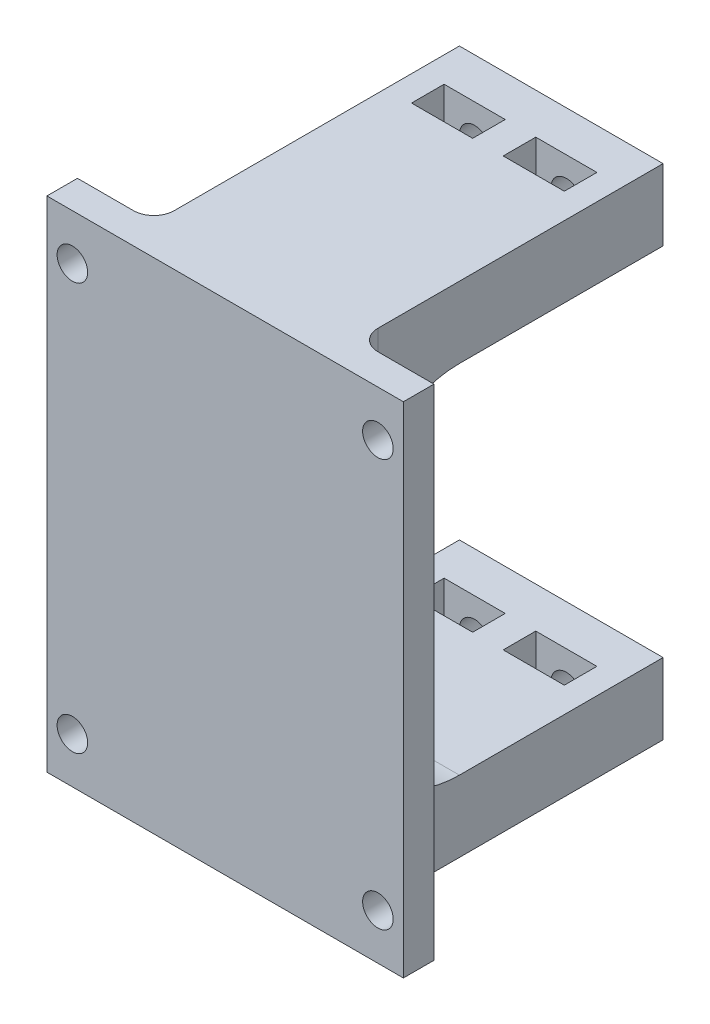
SolidWorks part; units mm, degrees
ref_plane "Front Plane" through (0, 0, 0) normal (0, 0, 1) x (1, 0, 0)
ref_plane "Top Plane" through (0, 0, 0) normal (0, 1, 0) x (1, 0, 0)
ref_plane "Right Plane" through (0, 0, 0) normal (1, 0, 0) x (0, 0, -1)
sketch "Sketch1" plane through (0, 0, 0) normal (0, 1, 0) x (1, 0, 0)
  line L1 (-10, 16.5) -> (10, 16.5)
  line L2 (-10, 16.5) -> (-10, -16.5)
  line L3 (-10, -16.5) -> (10, -16.5)
  line L4 (10, 16.5) -> (10, -16.5)
  line L5 (-17.5, -13.5) -> (17.5, -13.5)
  line L6 (-17.5, -13.5) -> (-17.5, -16.5)
  line L7 (-17.5, -16.5) -> (17.5, -16.5)
  line L8 (17.5, -13.5) -> (17.5, -16.5)
  point P4 (0, 16.5)
  point P6 (10, 0)
  point P11 (0, -13.5)
  dimension "D1" = 33
  dimension "D2" = 20
  dimension "D3" = 35
  dimension "D4" = 3
extrude "Boss-Extrude1" add sketch "Sketch1" along normal blind 49 contours L2 L5 L4 L1 | L7 L8 L5 L6 region at (0, 0, -1.5)
sketch "Sketch2" plane through (10, 0, 0) normal (1, 0, 0) x (0, 0, -1)
  line L0 (-13.5, 49) -> (-13.5, 0) construction
  line L1 (-13.5, 42) -> (16.5, 42)
  line L2 (-13.5, 42) -> (-13.5, 7)
  line L3 (-13.5, 7) -> (16.5, 7)
  line L4 (16.5, 42) -> (16.5, 7)
  line L5 (16.5, 49) -> (16.5, 0) construction
  line L6 (-13.5, 49) -> (-13.5, 0) construction
  point P10 (-13.5, 24.5)
  point P11 (16.5, 24.5)
  dimension "D1" = 35
extrude "Cut-Extrude1" cut sketch "Sketch2" against normal up to next
sketch "Sketch3" plane through (0, 0, 13.5) normal (0, 0, -1) x (-1, 0, 0)
  line L0 (-15, 44.5) -> (15, 44.5) construction
  line L1 (-15, 4.5) -> (15, 4.5) construction
  line L2 (10, 0) -> (-10, 0) construction
  line L3 (-10, 49) -> (-17.5, 49) construction
  circle A0 centre (-15, 44.5) radius 1.5
  circle A1 centre (15, 44.5) radius 1.5
  circle A2 centre (-15, 4.5) radius 1.5
  circle A3 centre (15, 4.5) radius 1.5
  point P8 (0, 44.5)
  point P9 (0, 4.5)
  dimension "D1" = 3
  dimension "D2" = 3
  dimension "D3" = 3
  dimension "D4" = 3
  dimension "D5" = 30
  dimension "D6" = 30
  dimension "D7" = 4.5
  dimension "D8" = 4.5
extrude "Cut-Extrude2" cut sketch "Sketch3" against normal up to next
fillet "Fillet1" radius 10 2 edges at (0, 7, 13.5) (0, 42, 13.5)
fillet "Fillet2" radius 2 4 edges at (-10, 40.5, 13.5) (-10, 8.5, 13.5) (10, 40.5, 13.5) (10, 8.5, 13.5)
sketch "Sketch4" plane through (0, 49, 0) normal (0, 1, 0) x (1, 0, 0)
  line L0 (-10, 16.5) -> (10, 16.5) construction
  line L1 (-7.5, 12.5) -> (7.5, 12.5)
  line L2 (-7.5, 12.5) -> (-7.5, 9.3)
  line L3 (-7.5, 9.3) -> (7.5, 9.3)
  line L4 (7.5, 12.5) -> (7.5, 9.3)
  line L6 (-7.5, 12.5) -> (-1.5, 12.5)
  line L7 (-7.5, 12.5) -> (-7.5, 9.3)
  line L8 (-7.5, 9.3) -> (-1.5, 9.3)
  line L9 (-1.5, 12.5) -> (-1.5, 9.3)
  line L10 (7.5, 12.5) -> (1.5, 12.5)
  line L11 (7.5, 12.5) -> (7.5, 9.3)
  line L12 (7.5, 9.3) -> (1.5, 9.3)
  line L13 (1.5, 12.5) -> (1.5, 9.3)
  point P4 (0, 12.5)
  dimension "D1" = 4
  dimension "D2" = 3.2
  dimension "D3" = 15
  dimension "D4" = 6
  dimension "D5" = 6
extrude "Cut-Extrude3" cut sketch "Sketch4" against normal through all contours L9 L1 L2 L3 | L1 L13 L3 L4 region at (-4.5, 49, -10.9) region at (4.5, 49, -10.9)
sketch "Sketch5" plane through (0, 0, -9.3) normal (0, 0, -1) x (-1, 0, 0)
  line L0 (7.5, 49) -> (1.5, 42) construction
  line L1 (1.5, 42) -> (7.5, 42) construction
  line L2 (7.5, 42) -> (1.5, 49) construction
  line L3 (1.5, 49) -> (7.5, 49) construction
  line L4 (7.5, 7) -> (1.5, 0) construction
  line L5 (1.5, 0) -> (7.5, 0) construction
  line L6 (7.5, 0) -> (1.5, 7) construction
  line L7 (1.5, 7) -> (7.5, 7) construction
  circle A0 centre (4.5, 45.5) radius 1.5
  circle A1 centre (4.5, 3.5) radius 1.5
  dimension "D1" = 3
  dimension "D2" = 3
extrude "Cut-Extrude4" cut sketch "Sketch5" along normal through all and the other way blind 15
mirror "Mirror1" about plane through (0, 0, 0) normal (1, 0, 0) of "Cut-Extrude4"
sketch "Sketch6" plane through (0, 0, 13.5) normal (0, 0, -1) x (-1, 0, 0)
  line L1 (-12, 32) -> (12, 32)
  line L2 (-12, 32) -> (-12, 17)
  line L3 (-12, 17) -> (12, 17)
  line L4 (12, 32) -> (12, 17)
extrude "Cut-Extrude5" [suppressed] cut sketch "Sketch6" against normal through all
